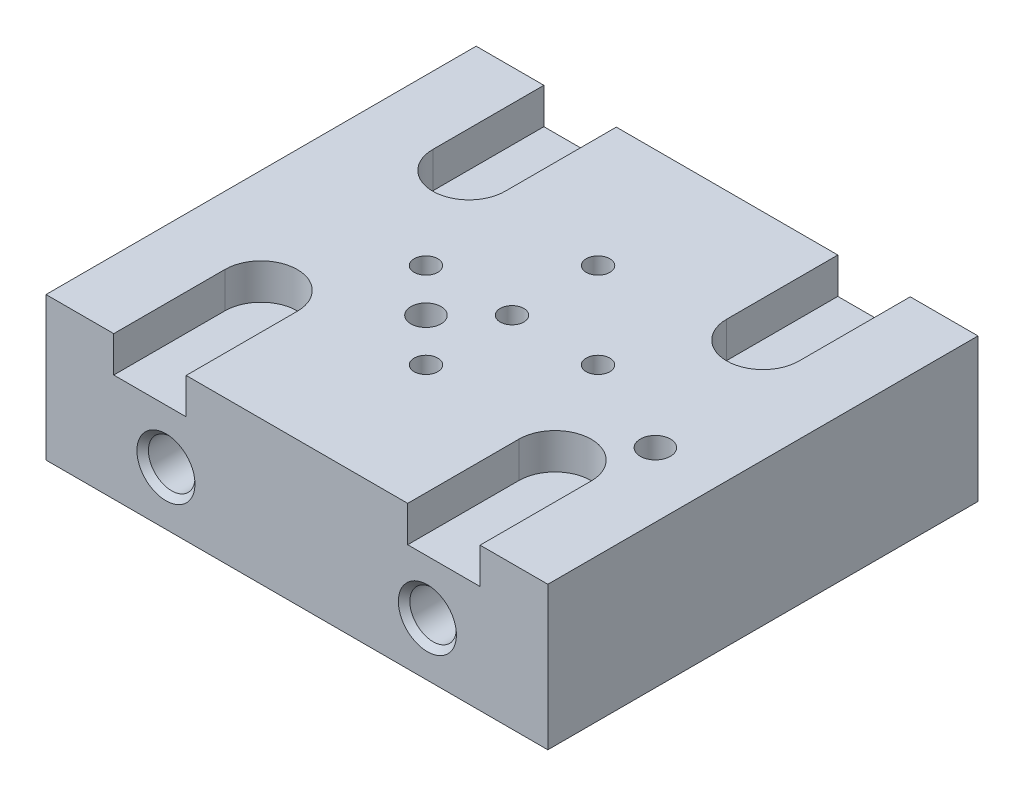
SolidWorks part; units mm, degrees
ref_plane "Front Plane" through (0, 0, 0) normal (0, 0, 1) x (1, 0, 0)
ref_plane "Top Plane" through (0, 0, 0) normal (0, 1, 0) x (1, 0, 0)
ref_plane "Right Plane" through (0, 0, 0) normal (1, 0, 0) x (0, 0, -1)
sketch "Sketch3" plane through (0, 0, 0) normal (0, 1, 0) x (1, 0, 0)
  line L1 (0, 0) -> (70, 0)
  line L2 (0, 0) -> (0, -60)
  line L3 (0, -60) -> (70, -60)
  line L4 (70, 0) -> (70, -60)
  dimension "D1" = 70
  dimension "D2" = 60
extrude "Boss-Extrude3" add sketch "Sketch3" along normal blind 20
sketch "Sketch4" plane through (0, 20, 0) normal (0, 1, 0) x (1, 0, 0)
  line L0 (35, 0) -> (35, -60) construction
  line L1 (70, 0) -> (0, 0) construction
  line L2 (0, -60) -> (70, -60) construction
  line L3 (0, -30) -> (70, -30) construction
  line L4 (0, 0) -> (0, -60) construction
  line L5 (70, -60) -> (70, 0) construction
  line L6 (21.35, -30) -> (21.35, 0) construction
  line L7 (0, 0) -> (70, 0) construction
  line L8 (24.65, -30) -> (24.65, 0) construction
  line L9 (45.35, -30) -> (45.35, 0) construction
  line L10 (48.65, -30) -> (48.65, 0) construction
  circle A0 centre (35, -30) radius 1.65
  circle A1 centre (35, -18) radius 1.65
  circle A2 centre (47, -30) radius 1.65
  circle A3 centre (35, -42) radius 1.65
  circle A4 centre (23, -30) radius 1.65
  dimension "D1" = 3.3
  dimension "D2" = 12
  dimension "D3" = 12
  dimension "D4" = 12
  dimension "D5" = 12
extrude "Cut-Extrude1" cut sketch "Sketch4" against normal through all
sketch "Sketch6" plane through (0, 0, 0) normal (0, -1, 0) x (1, 0, 0)
  line L0 (70, 30) -> (0, 30) construction
  line L1 (55, 24) -> (35, 24) construction
  line L2 (67, 24) -> (70, 24) construction
  line L3 (70, 60) -> (70, 0) construction
  line L4 (0, 0) -> (0, 60) construction
  line L5 (29, 24) -> (29, 0) construction
  line L6 (70, 0) -> (0, 0) construction
  line L7 (61, 24) -> (61, 0) construction
  line L8 (35, 24) -> (35, 0) construction
  line L9 (55, 24) -> (55, 0) construction
  line L10 (23, 24) -> (23, 0) construction
  line L11 (67, 24) -> (67, 0) construction
  line L12 (58.9, 24) -> (58.9, 0) construction
  line L13 (63.1, 24) -> (63.1, 0) construction
  line L14 (31.1, 24) -> (31.1, 0) construction
  line L15 (26.9, 24) -> (26.9, 0) construction
  line L16 (35, 0) -> (35, 60) construction
  line L17 (34.9322, 16.3514) -> (34.9322, 0) construction
  line L18 (34.9322, 43.6486) -> (34.9322, 60) construction
  line L19 (26.9, 36) -> (26.9, 60) construction
  line L20 (31.1, 36) -> (31.1, 60) construction
  line L21 (63.1, 36) -> (63.1, 60) construction
  line L22 (58.9, 36) -> (58.9, 60) construction
  line L23 (67, 36) -> (67, 60) construction
  line L24 (23, 36) -> (23, 60) construction
  line L25 (55, 36) -> (55, 60) construction
  line L26 (35, 36) -> (35, 60) construction
  line L27 (61, 36) -> (61, 60) construction
  line L28 (29, 36) -> (29, 60) construction
  line L29 (67, 36) -> (70, 36) construction
  line L30 (55, 36) -> (35, 36) construction
  circle A2 centre (61, 24) radius 6 construction
  circle A3 centre (29, 24) radius 6 construction
  circle A4 centre (61, 24) radius 2.1
  circle A5 centre (29, 24) radius 2.1
  circle A6 centre (35, 18) radius 1.65 construction
  circle A7 centre (29, 36) radius 6 construction
  circle A8 centre (61, 36) radius 6 construction
  circle A9 centre (29, 36) radius 2.1
  circle A10 centre (61, 36) radius 2.1
  dimension "D1" = 12
  dimension "D2" = 20
  dimension "D3" = 4.2
extrude "Cut-Extrude2" cut sketch "Sketch6" against normal through all contours A9 | A10 region at (29, 0, 36) region at (61, 0, 36)
sketch "Sketch9" plane through (0, 0, 60) normal (0, 0, -1) x (-1, 0, 0)
  line L0 (-29, 0) -> (-29, 20) construction
  line L1 (-70, 20) -> (0, 20) construction
  line L2 (-61, 0) -> (-61, 20) construction
  line L3 (-67, 0) -> (-55, 0) construction
  line L4 (-23, 0) -> (-23, 20) construction
  line L5 (-35, 0) -> (-35, 20) construction
  line L6 (-55, 0) -> (-55, 20) construction
  line L7 (-67, 0) -> (-67, 20) construction
  line L8 (-58.9, 0) -> (-58.9, 20) construction
  line L9 (-63.1, 0) -> (-63.1, 20) construction
  line L10 (-31.1, 0) -> (-31.1, 20) construction
  line L11 (-26.9, 0) -> (-26.9, 20) construction
  line L12 (-58.9, 7.5) -> (-56.45, 7.5) construction
  line L13 (-53.2, 10.75) -> (-53.2, 20) construction
  line L14 (-13.4822, 7.5) -> (0, 7.5) construction
  line L15 (-19.9822, 7.5) -> (-21.35, 7.5) construction
  line L16 (-16.7322, 20) -> (-16.7322, 10.75) construction
  line L17 (0, 20) -> (0, 0) construction
  line L18 (-34.9322, 0) -> (-34.9322, 20) construction
  line L19 (-34.9322, 0) -> (-34.9322, 20) construction
  line L20 (-49.95, 7.5) -> (-34.9322, 7.5) construction
  line L21 (-21.35, 20) -> (-21.35, 0) construction
  line L22 (0, 0) -> (-70, 0) construction
  line L23 (-24.65, 20) -> (-24.65, 0) construction
  line L24 (-45.35, 20) -> (-45.35, 0) construction
  line L25 (-48.65, 20) -> (-48.65, 0) construction
  line L26 (0, 7.5) -> (0, 20) construction
  circle A0 centre (-53.2, 7.5) radius 3.25
  circle A1 centre (-16.7322, 7.5) radius 3.25
  dimension "D1" = 6.5
  dimension "D2" = 18.2
  dimension "D3" = 18.2
  dimension "D4" = 12.5
extrude "Cut-Extrude3" cut sketch "Sketch9" along normal blind 40.25
sketch "Sketch11" plane through (0, 0, 0) normal (0, -1, 0) x (1, 0, 0)
  line L0 (70, 30) -> (0, 30) construction
  circle A0 centre (23, 30) radius 3
  circle A1 centre (35, 42) radius 3
  circle A2 centre (35, 30) radius 3
  circle A3 centre (35, 18) radius 3
  circle A4 centre (47, 30) radius 3
  circle M3 centre (35, 18) radius 1.65
  circle M4 centre (47, 30) radius 1.65
  circle M5 centre (35, 42) radius 1.65
  circle M6 centre (23, 30) radius 1.65
  circle M7 centre (35, 30) radius 1.65
  dimension "D1" = 6
extrude "Cut-Extrude4" cut sketch "Sketch11" against normal blind 3 contours A3 M3 | A2 M7 | A4 M4 | A0 M6 | A1 M5 | M5 | M6 | M7 | M4 | M3 | A3 region at (20.0849, 0, 30) region at (32.0849, 0, 42) region at (32.0849, 0, 30) region at (32.0849, 0, 18) region at (44.0849, 0, 30) region at (35, 0, 18) region at (47, 0, 30) region at (35, 0, 42) region at (23, 0, 30) region at (35, 0, 30)
sketch "Sketch12" plane through (0, 20, 0) normal (0, 1, 0) x (1, 0, 0)
  line L0 (35, -60.1049) -> (14.5, -60.1049) construction
  line L1 (35, 0.1049) -> (35, -60.1049) construction
  line L2 (14.5, -60.1049) -> (14.5, -44.5) construction
  line L3 (9.45, -60.1049) -> (9.45, -44.5)
  line L4 (19.55, -60.1049) -> (19.55, -44.5)
  line L5 (70, -30) -> (0, -30) construction
  line L6 (35, 0) -> (35, -60) construction
  line L7 (35, 0.1049) -> (14.5, 0.1049) construction
  line L8 (55.5, -60.1049) -> (55.5, -44.5) construction
  line L9 (60.55, -60.1049) -> (60.55, -44.5)
  line L10 (50.45, -60.1049) -> (50.45, -44.5)
  line L11 (55.5, 0.1049) -> (55.5, -15.5) construction
  line L12 (60.55, 0.1049) -> (60.55, -15.5)
  line L13 (50.45, 0.1049) -> (50.45, -15.5)
  line L14 (14.5, 0.1049) -> (14.5, -15.5) construction
  line L15 (9.45, 0.1049) -> (9.45, -15.5)
  line L16 (19.55, 0.1049) -> (19.55, -15.5)
  arc A0 (9.45, -60.1049) -> (19.55, -60.1049) centre (14.5, -60.1049) ccw
  arc A1 (19.55, -44.5) -> (9.45, -44.5) centre (14.5, -44.5) ccw
  arc A3 (60.55, -60.1049) -> (50.45, -60.1049) centre (55.5, -60.1049) cw
  arc A4 (50.45, -44.5) -> (60.55, -44.5) centre (55.5, -44.5) cw
  arc A6 (60.55, 0.1049) -> (50.45, 0.1049) centre (55.5, 0.1049) ccw
  arc A7 (50.45, -15.5) -> (60.55, -15.5) centre (55.5, -15.5) ccw
  arc A8 (9.45, 0.1049) -> (19.55, 0.1049) centre (14.5, 0.1049) cw
  arc A9 (19.55, -15.5) -> (9.45, -15.5) centre (14.5, -15.5) cw
  point P0 (14.5, -52.3025)
  point P19 (35, -30)
  point P23 (55.5, -52.3025)
  point P29 (55.5, -7.6975)
  point P36 (14.5, -7.6975)
  dimension "D4" = 5.05
  dimension "D1" = 20.5
extrude "Cut-Extrude5" cut sketch "Sketch12" against normal blind 5
chamfer "Chamfer1" distance 0.8 angle 45 2 edges at (13.4822, 7.5, 60) (49.95, 7.5, 60)
